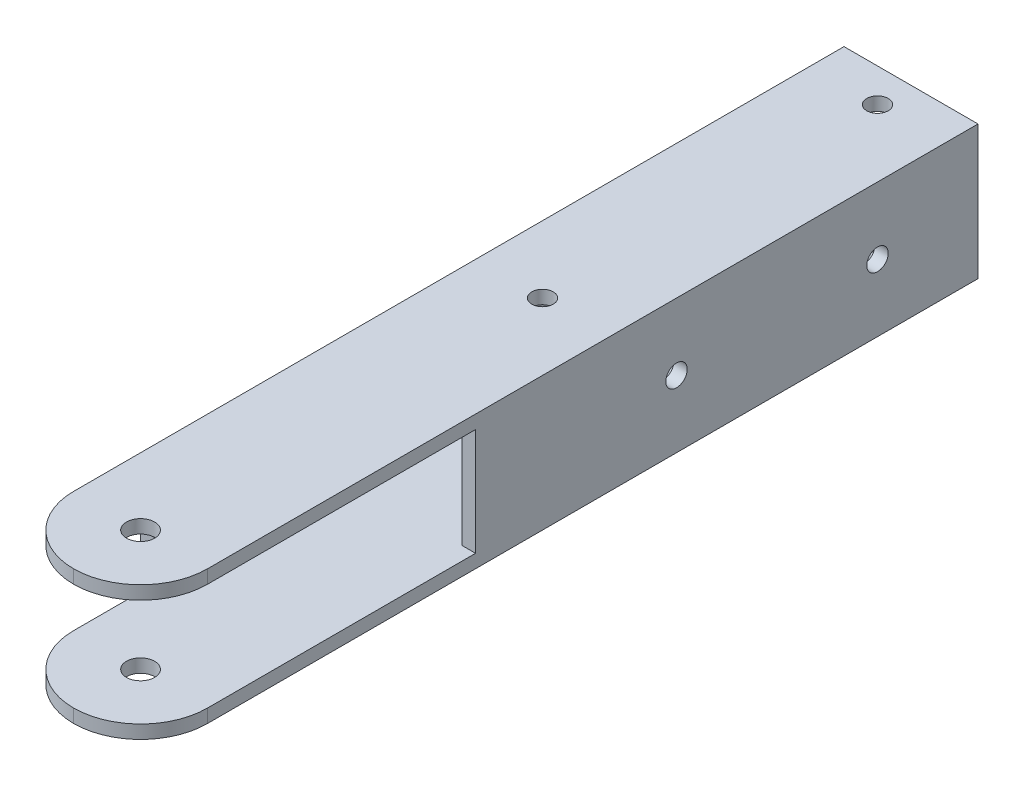
SolidWorks part; units mm, degrees
ref_plane "正面" through (0, 0, 0) normal (0, 0, 1) x (1, 0, 0)
ref_plane "平面" through (0, 0, 0) normal (0, 1, 0) x (1, 0, 0)
ref_plane "右側面" through (0, 0, 0) normal (1, 0, 0) x (0, 0, -1)
sketch "ｽｹｯﾁ1" plane through (0, 0, 0) normal (0, 0, 1) x (1, 0, 0)
  line L0 (-8, 8) -> (-8, -8)
  line L1 (-10, 10) -> (10, 10)
  line L2 (-10, 10) -> (-10, -10)
  line L3 (-10, -10) -> (10, -10)
  line L4 (10, 10) -> (10, -10)
  line L5 (-10, 10) -> (10, -10) construction
  line L6 (-10, -10) -> (10, 10) construction
  line L7 (-8, -8) -> (8, -8)
  line L8 (8, 8) -> (8, -8)
  line L9 (-8, 8) -> (8, 8)
  point P0 (0, 0)
  dimension "D1" = 20
  dimension "D2" = 20
  dimension "D3" = 2
extrude "ﾎﾞｽ - 押し出し1" add sketch "ｽｹｯﾁ1" along normal blind 125
sketch "ｽｹｯﾁ2" plane through (0, 10, 0) normal (0, 1, 0) x (1, 0, 0)
  line L0 (10, -125) -> (-10, -125) construction
  line L1 (10, 0) -> (-10, 0) construction
  circle A0 centre (0, -5) radius 1.6
  circle A1 centre (0, -55) radius 1.6
  circle A2 centre (0, -115) radius 2.1
  dimension "D1" = 55
  dimension "D2" = 3.2
  dimension "D3" = 5
  dimension "D4" = 3.2
  dimension "D5" = 10
  dimension "D6" = 4.2
extrude "ｶｯﾄ - 押し出し1" cut sketch "ｽｹｯﾁ2" against normal blind 408.3717
sketch "ｽｹｯﾁ3" plane through (10, 0, 0) normal (1, 0, 0) x (0, 0, -1)
  line L1 (0, -10) -> (0, 10) construction
  circle A0 centre (-15, 0) radius 1.6
  circle A1 centre (-45, 0) radius 1.6
  dimension "D1" = 3.2
  dimension "D2" = 3.2
  dimension "D3" = 45
  dimension "D4" = 15
extrude "ｶｯﾄ - 押し出し2" cut sketch "ｽｹｯﾁ3" against normal blind 10
sketch "ｽｹｯﾁ5" plane through (10, 0, 0) normal (1, 0, 0) x (0, 0, -1)
  line L0 (-125, -10) -> (-125, 10) construction
  line L1 (-125, -8) -> (-75, -8)
  line L2 (-125, -8) -> (-125, 8)
  line L3 (-125, 8) -> (-75, 8)
  line L4 (-75, -8) -> (-75, 8)
  line L5 (-125, -10) -> (0, -10) construction
  line L6 (-125, 10) -> (0, 10) construction
  dimension "D1" = 50
  dimension "D2" = 2
  dimension "D3" = 2
extrude "ｶｯﾄ - 押し出し3" cut sketch "ｽｹｯﾁ5" against normal through all
sketch "ｽｹｯﾁ6" plane through (-10, 0, 0) normal (-1, 0, 0) x (0, 0, 1)
  line L0 (125, -8) -> (75, -8) construction
  line L1 (75, 8) -> (105, 8)
  line L2 (75, 8) -> (75, -8)
  line L3 (75, -8) -> (105, -8)
  line L4 (105, 8) -> (105, -8)
  line L6 (75, -8) -> (75, 8) construction
  dimension "D1" = 30
  dimension "D2" = 0
extrude "ﾎﾞｽ - 押し出し2" add sketch "ｽｹｯﾁ6" against normal blind 2
fillet "ﾌｨﾚｯﾄ1" radius 10 4 edges at (-10, 9, 125) (10, 9, 125) (10, -9, 125) (-10, -9, 125)
